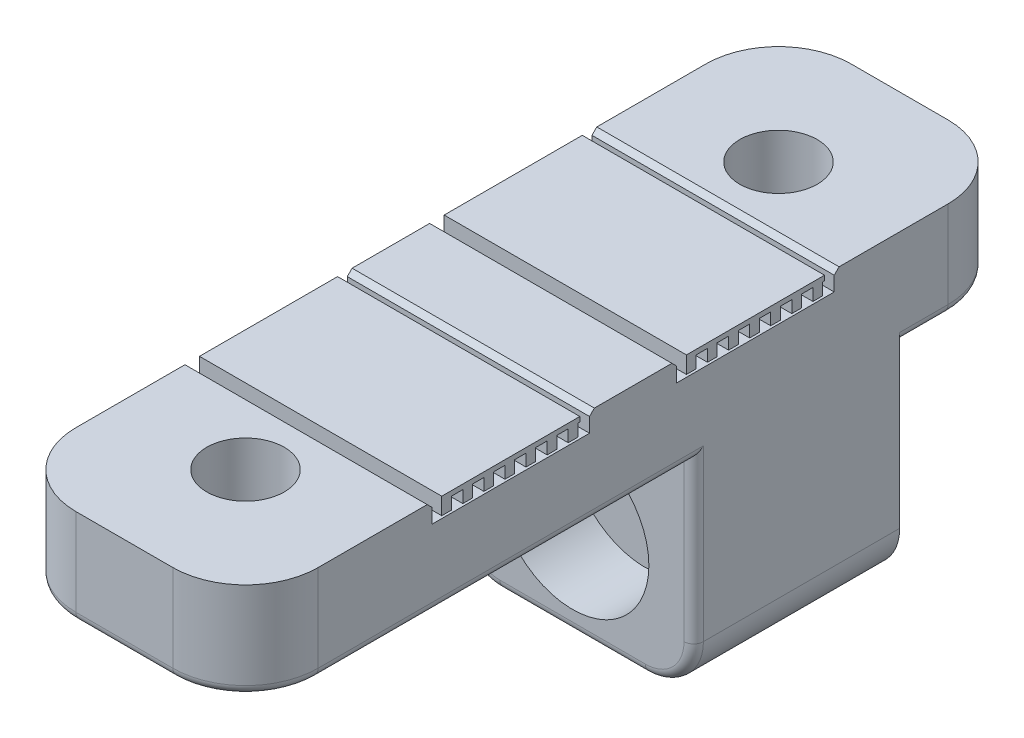
SolidWorks part; units mm, degrees
ref_plane "前视基准面" through (0, 0, 0) normal (0, 0, 1) x (1, 0, 0)
ref_plane "上视基准面" through (0, 0, 0) normal (0, 1, 0) x (1, 0, 0)
ref_plane "右视基准面" through (0, 0, 0) normal (1, 0, 0) x (0, 0, -1)
other "Configuration Table"
sketch "草图1" plane through (0, 0, 0) normal (0, 1, 0) x (1, 0, 0)
  line L1 (0, 0) -> (10, 0)
  line L2 (0, 0) -> (0, 32)
  line L3 (0, 32) -> (10, 32)
  line L4 (10, 0) -> (10, 32)
  circle A0 centre (5, 27) radius 1.6
  circle A1 centre (5, 5) radius 1.6
  point P7 (10, 16)
  dimension "D3" = 3.2
  dimension "D5" = 11
  dimension "D1" = 10
  dimension "D2" = 32
  dimension "D4" = 2
extrude "凸台-拉伸1" add sketch "草图1" along normal blind 4
sketch "草图2" plane through (0, 0, 0) normal (0, -1, 0) x (-1, 0, 0)
  line L0 (0, 32) -> (0, 0) construction
  line L1 (0, 18.5) -> (-10, 18.5)
  line L2 (0, 18.5) -> (0, 27)
  line L3 (0, 27) -> (-10, 27)
  line L4 (-10, 18.5) -> (-10, 27)
  line L5 (-10, 0) -> (-10, 32) construction
  circle A0 centre (-5, 27) radius 1.6 construction
  dimension "D1" = 8.5
  dimension "D2" = 0
extrude "凸台-拉伸2" add sketch "草图2" along normal blind 8.6
sketch "草图3" plane through (0, 0, -18.5) normal (0, 0, 1) x (1, 0, 0)
  line L0 (0, -8.6) -> (0, 0) construction
  line L3 (10, -8.6) -> (0, -8.6) construction
  circle A0 centre (5, -4.6) radius 3.15
  point P6 (6.4235, -10)
  dimension "D1" = 6.3
  dimension "D3" = 4
  dimension "D2" = 5
extrude "切除-拉伸1" cut sketch "草图3" against normal blind 3
sketch "草图4" plane through (0, 0, 0) normal (0, -1, 0) x (-1, 0, 0)
  line L0 (0, 27) -> (-10, 27) construction
  circle A0 centre (-5, 27) radius 3
  dimension "D1" = 6
extrude "切除-拉伸2" cut sketch "草图4" along normal through all
sketch "草图5" plane through (0, 4, 0) normal (0, 1, 0) x (1, 0, 0)
  line L0 (0, 32) -> (0, 0) construction
  line L1 (0, 24.3) -> (10, 24.3)
  line L2 (0, 24.3) -> (0, 17.8)
  line L3 (0, 17.8) -> (10, 17.8)
  line L4 (10, 24.3) -> (10, 17.8)
  line L5 (10, 0) -> (10, 32) construction
  line L7 (0, 14.2) -> (10, 14.2)
  line L8 (0, 14.2) -> (0, 7.7)
  line L9 (0, 7.7) -> (10, 7.7)
  line L10 (10, 14.2) -> (10, 7.7)
  circle A0 centre (5, 27) radius 1.6 construction
  circle A1 centre (5, 5) radius 1.6 construction
  dimension "D1" = 2.7
  dimension "D2" = 2.7
  dimension "D3" = 6.5
  dimension "D4" = 6.5
extrude "切除-拉伸3" cut sketch "草图5" against normal blind 0.8
sketch "草图8" plane through (0, 0, 0) normal (0, -1, 0) x (-1, 0, 0)
  circle A0 centre (-5, 5) radius 3
  circle A1 centre (-5, 27) radius 3
  dimension "D1" = 6
  dimension "D2" = 6
fillet "圆角1" radius 3 4 edges at (10, 2, 0) (0, 2, 0) (10, 2, -32) (0, 2, -32)
fillet "圆角2" radius 2 2 edges at (0, -8.6, -22.75) (10, -8.6, -22.75)
fillet "圆角3" radius 1 2 edges at (2, -4.3, -27) (8, -4.3, -27)
chamfer "倒角1" distance 0.2 angle 45 4 edges at (5, 4, -24.3) (5, 4, -17.8) (5, 4, -14.2) (5, 4, -7.7)
fillet "圆角5" radius 0.4 15 edges at (0, 0, -28) (10, 0, -28) (9.1213, 0, -31.1213) (5, 0, -32) (10, 0, -10.75) (9.1213, 0, -0.8787) (5, 0, 0) (0.8787, 0, -0.8787) (10, -3.3, -18.5) (9.4142, -8.0142, -18.5) (5, -8.6, -18.5) (0.5858, -8.0142, -18.5) (0.8787, 0, -31.1213) (0, 0, -10.75) (0, -3.3, -18.5)
sketch "草图6" plane through (0, 4, 0) normal (0, 1, 0) x (1, 0, 0)
  line L0 (0, 14.2) -> (0, 7.7) construction
  line L1 (0, 13.8) -> (10, 13.8)
  line L2 (0, 13.8) -> (0, 8.1)
  line L3 (0, 8.1) -> (10, 8.1)
  line L4 (10, 13.8) -> (10, 8.1)
  line L5 (10, 7.7) -> (10, 14.2) construction
  line L6 (0, 24.3) -> (0, 17.8) construction
  line L7 (0, 23.9) -> (10, 23.9)
  line L8 (0, 23.9) -> (0, 18.2)
  line L9 (0, 18.2) -> (10, 18.2)
  line L10 (10, 23.9) -> (10, 18.2)
  line L11 (10, 24.3) -> (0, 24.3) construction
  line L13 (0, 17.8) -> (10, 17.8) construction
  line L14 (10, 14.2) -> (0, 14.2) construction
  line L15 (0, 7.7) -> (10, 7.7) construction
  point P17 (0, 0)
  dimension "D1" = 0.4
  dimension "D2" = 0.4
  dimension "D3" = 0.4
  dimension "D4" = 0.4
extrude "凸台-拉伸3" add sketch "草图6" against normal blind 0.2 separate body
sketch "草图7" plane through (0, 4, 0) normal (0, 1, 0) x (1, 0, 0)
  line L0 (10, 8.1) -> (10, 13.8) construction
  line L1 (0, 8.1) -> (10, 8.1)
  line L2 (0, 8.1) -> (0, 8.5)
  line L3 (0, 8.5) -> (10, 8.5)
  line L4 (10, 8.1) -> (10, 8.5)
  line L5 (10, 18.2) -> (10, 23.9) construction
  line L6 (0, 18.2) -> (10, 18.2)
  line L7 (0, 18.2) -> (0, 18.6)
  line L8 (0, 18.6) -> (10, 18.6)
  line L9 (10, 18.2) -> (10, 18.6)
  line L10 (0, 19.07) -> (0, 19.47)
  line L11 (0, 19.07) -> (10, 19.07)
  line L12 (10, 19.07) -> (10, 19.47)
  line L13 (0, 19.47) -> (10, 19.47)
  line L14 (0, 8.97) -> (0, 9.37)
  line L15 (0, 8.97) -> (10, 8.97)
  line L16 (10, 8.97) -> (10, 9.37)
  line L17 (0, 9.37) -> (10, 9.37)
  line L18 (0, 19.94) -> (0, 20.34)
  line L19 (0, 19.94) -> (10, 19.94)
  line L20 (10, 19.94) -> (10, 20.34)
  line L21 (0, 20.34) -> (10, 20.34)
  line L22 (0, 9.84) -> (0, 10.24)
  line L23 (0, 9.84) -> (10, 9.84)
  line L24 (10, 9.84) -> (10, 10.24)
  line L25 (0, 10.24) -> (10, 10.24)
  line L26 (0, 20.81) -> (0, 21.21)
  line L27 (0, 20.81) -> (10, 20.81)
  line L28 (10, 20.81) -> (10, 21.21)
  line L29 (0, 21.21) -> (10, 21.21)
  line L30 (0, 10.71) -> (0, 11.11)
  line L31 (0, 10.71) -> (10, 10.71)
  line L32 (10, 10.71) -> (10, 11.11)
  line L33 (0, 11.11) -> (10, 11.11)
  line L34 (0, 21.68) -> (0, 22.08)
  line L35 (0, 21.68) -> (10, 21.68)
  line L36 (10, 21.68) -> (10, 22.08)
  line L37 (0, 22.08) -> (10, 22.08)
  line L38 (0, 11.58) -> (0, 11.98)
  line L39 (0, 11.58) -> (10, 11.58)
  line L40 (10, 11.58) -> (10, 11.98)
  line L41 (0, 11.98) -> (10, 11.98)
  line L42 (0, 22.55) -> (0, 22.95)
  line L43 (0, 22.55) -> (10, 22.55)
  line L44 (10, 22.55) -> (10, 22.95)
  line L45 (0, 22.95) -> (10, 22.95)
  line L46 (0, 12.45) -> (0, 12.85)
  line L47 (0, 12.45) -> (10, 12.45)
  line L48 (10, 12.45) -> (10, 12.85)
  line L49 (0, 12.85) -> (10, 12.85)
  line L50 (0, 23.42) -> (0, 23.82)
  line L51 (0, 23.42) -> (10, 23.42)
  line L52 (10, 23.42) -> (10, 23.82)
  line L53 (0, 23.82) -> (10, 23.82)
  line L54 (0, 13.32) -> (0, 13.72)
  line L55 (0, 13.32) -> (10, 13.32)
  line L56 (10, 13.32) -> (10, 13.72)
  line L57 (0, 13.72) -> (10, 13.72)
  dimension "D1" = 0.4
  dimension "D2" = 0.4
  dimension "D3" = 7
extrude "凸台-拉伸4" add sketch "草图7" against normal blind 0.7
extrude "切除-拉伸4" cut sketch "草图8" against normal blind 0.8
